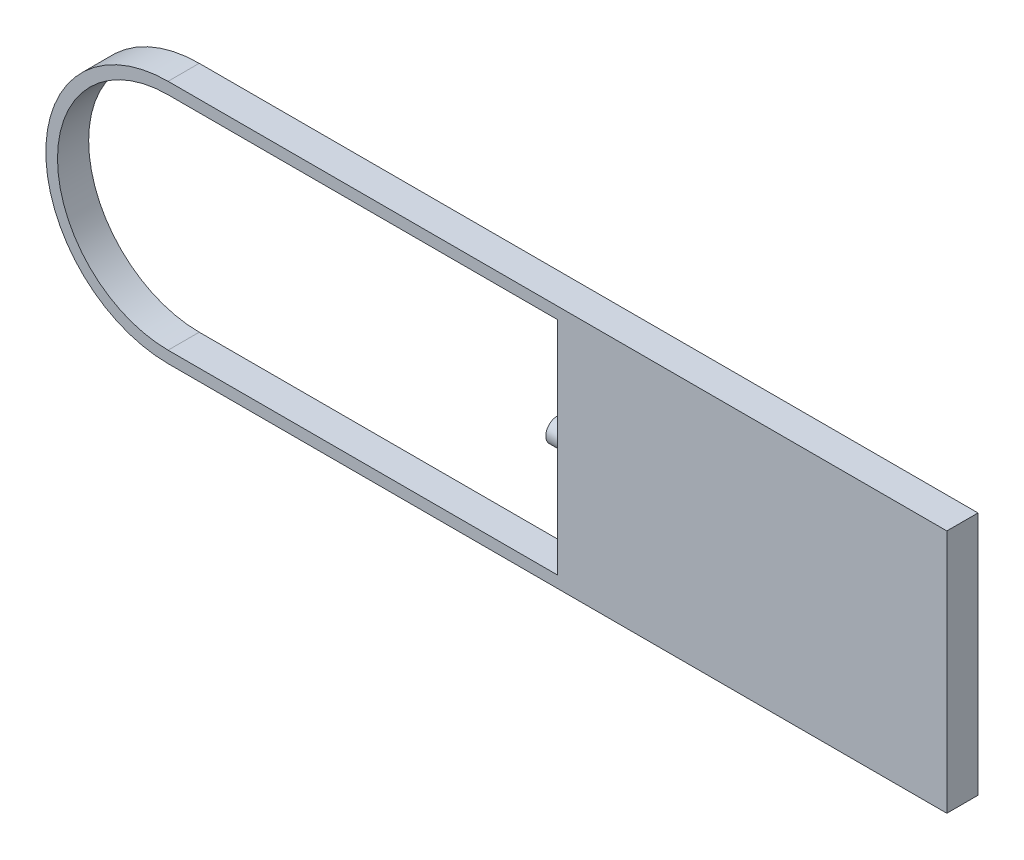
SolidWorks part; units mm, degrees
ref_plane "Front Plane" through (0, 0, 0) normal (0, 0, 1) x (1, 0, 0)
ref_plane "Top Plane" through (0, 0, 0) normal (0, 1, 0) x (1, 0, 0)
ref_plane "Right Plane" through (0, 0, 0) normal (1, 0, 0) x (0, 0, -1)
sketch "Sketch1" plane through (0, 0, 0) normal (0, 0, 1) x (1, 0, 0)
  circle A0 centre (0, 0) radius 19.939
  dimension "D1" = 39.878
extrude "circle extrude" add sketch "Sketch1" along normal blind 5.08
sketch "Sketch3" plane through (0, 0, 0) normal (1, 0, 0) x (0, 0, -1)
  line L0 (0, 55) -> (0, -55) construction
  line L1 (-5.08, 19.939) -> (0, 19.939)
  line L2 (-5.08, 19.939) -> (-5.08, -19.939)
  line L3 (-5.08, -19.939) -> (0, -19.939)
  line L4 (0, 19.939) -> (0, -19.939)
  line L5 (-5.08, -19.939) -> (0, -19.939) construction
extrude "rectangle extrude" add sketch "Sketch3" along normal blind 127
sketch "Sketch2" plane through (0, 0, 5.08) normal (0, 0, 1) x (1, 0, 0)
  circle A0 centre (0, 0) radius 18.034
  dimension "D1" = 36.068
extrude "circle cut" cut sketch "Sketch2" against normal through all
sketch "Sketch6" plane through (0, 0, 5.08) normal (0, 0, 1) x (1, 0, 0)
  line L1 (125.095, -18.034) -> (125.095, 18.034)
  line L3 (0, -18.034) -> (0, 18.034)
  line L4 (0, -18.034) -> (125.095, -18.034)
  line L5 (127, -19.939) -> (0, -19.939) construction
  line L6 (0, 18.034) -> (125.095, 18.034)
  line L8 (127, 19.939) -> (127, -19.939) construction
  arc A0 (0, 19.939) -> (0, -19.939) centre (0, 0) ccw construction
  circle A1 centre (0, 0) radius 18.034 construction
  point P5 (125.095, 0)
  point P12 (0, 0)
  point P17 (-19.939, 0)
  dimension "D1" = 1.905
  dimension "D2" = 1.905
  dimension "D3" = 19.939
extrude "rectangle cut" cut sketch "Sketch6" against normal through all
sketch "Sketch7" plane through (0, 0, 5.08) normal (0, 0, 1) x (1, 0, 0)
  line L1 (63.5, 18.034) -> (125.095, 18.034)
  line L2 (125.095, -18.034) -> (125.095, 18.034) construction
  line L3 (125.095, 18.034) -> (125.095, -18.034)
  line L4 (125.095, -18.034) -> (63.5, -18.034)
  line L5 (63.5, 18.034) -> (63.5, -18.034)
  line L6 (125.095, 18.034) -> (0, 18.034) construction
  dimension "D2" = 63.5
extrude "end shape" add sketch "Sketch7" against normal blind 5.08
sketch "Sketch8" plane through (63.5, 0, 0) normal (-1, 0, 0) x (0, 0, 1)
  circle A0 centre (2.54, 0) radius 1.905
  point P2 (0, 0)
  dimension "D1" = 3.81
  dimension "D2" = 2.54
extrude "Boss-Extrude1" add sketch "Sketch8" along normal blind 2.54
